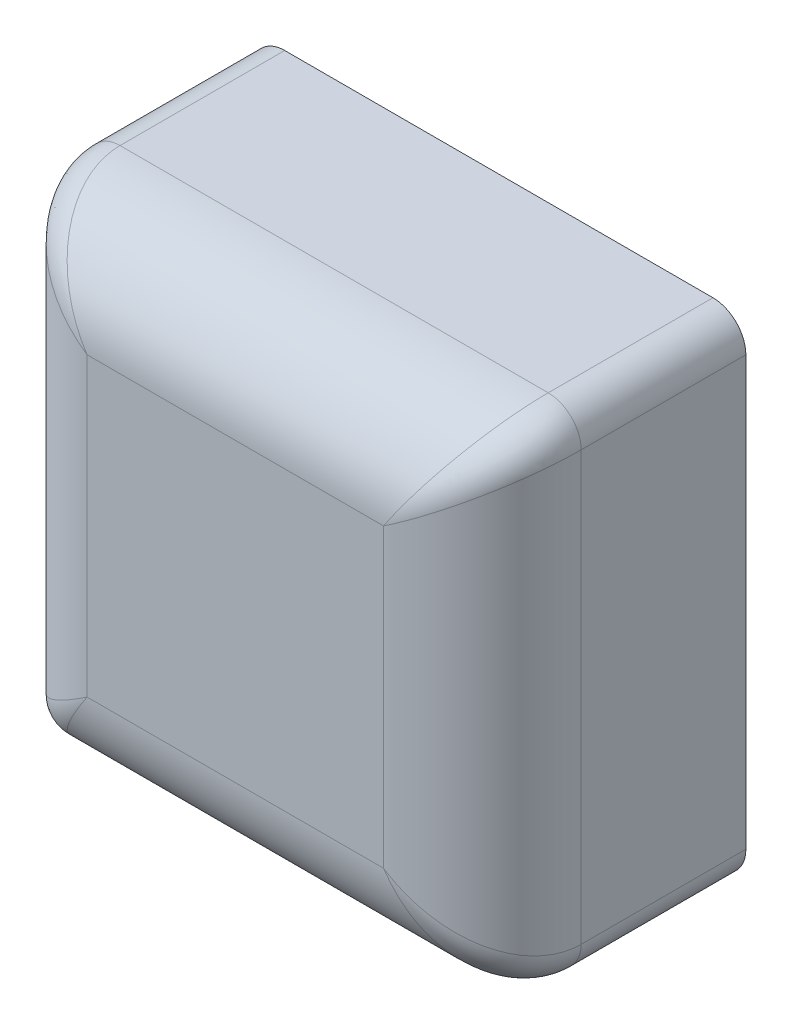
SolidWorks part; units mm, degrees
ref_plane "Front Plane" through (0, 0, 0) normal (0, 0, 1) x (1, 0, 0)
ref_plane "Top Plane" through (0, 0, 0) normal (0, 1, 0) x (1, 0, 0)
ref_plane "Right Plane" through (0, 0, 0) normal (1, 0, 0) x (0, 0, -1)
sketch "Base Sketch" plane through (0, 0, 0) normal (0, 0, 1) x (1, 0, 0)
  line L1 (-7.5, 7.5) -> (7.5, 7.5)
  line L2 (-7.5, 7.5) -> (-7.5, -7.5)
  line L3 (-7.5, -7.5) -> (7.5, -7.5)
  line L4 (7.5, 7.5) -> (7.5, -7.5)
  line L5 (-7.5, 7.5) -> (7.5, -7.5) construction
  line L6 (-7.5, -7.5) -> (7.5, 7.5) construction
  point P0 (0, 0)
  dimension "D1" = 15
  dimension "D2" = 15
extrude "Base Sketch Extrude" add sketch "Base Sketch" along normal blind 8
shell "Tip Cap Shell" thickness 1.5 removed face at (0, 0, 0)
fillet "Fillet1" radius 3 4 edges at (0, -7.5, 8) (-7.5, 0, 8) (0, 7.5, 8) (7.5, 0, 8)
fillet "Fillet2" radius 1 8 edges at (6.6213, 6.6213, 7.1213) (6.6213, -6.6213, 7.1213) (-6.6213, -6.6213, 7.1213) (-6.6213, 6.6213, 7.1213) (7.5, 7.5, 2.5) (7.5, -7.5, 2.5) (-7.5, -7.5, 2.5) (-7.5, 7.5, 2.5)
fillet "Fillet3" radius 2 4 edges at (6, -6, 3.25) (6, 6, 3.25) (-6, -6, 3.25) (-6, 6, 3.25)
